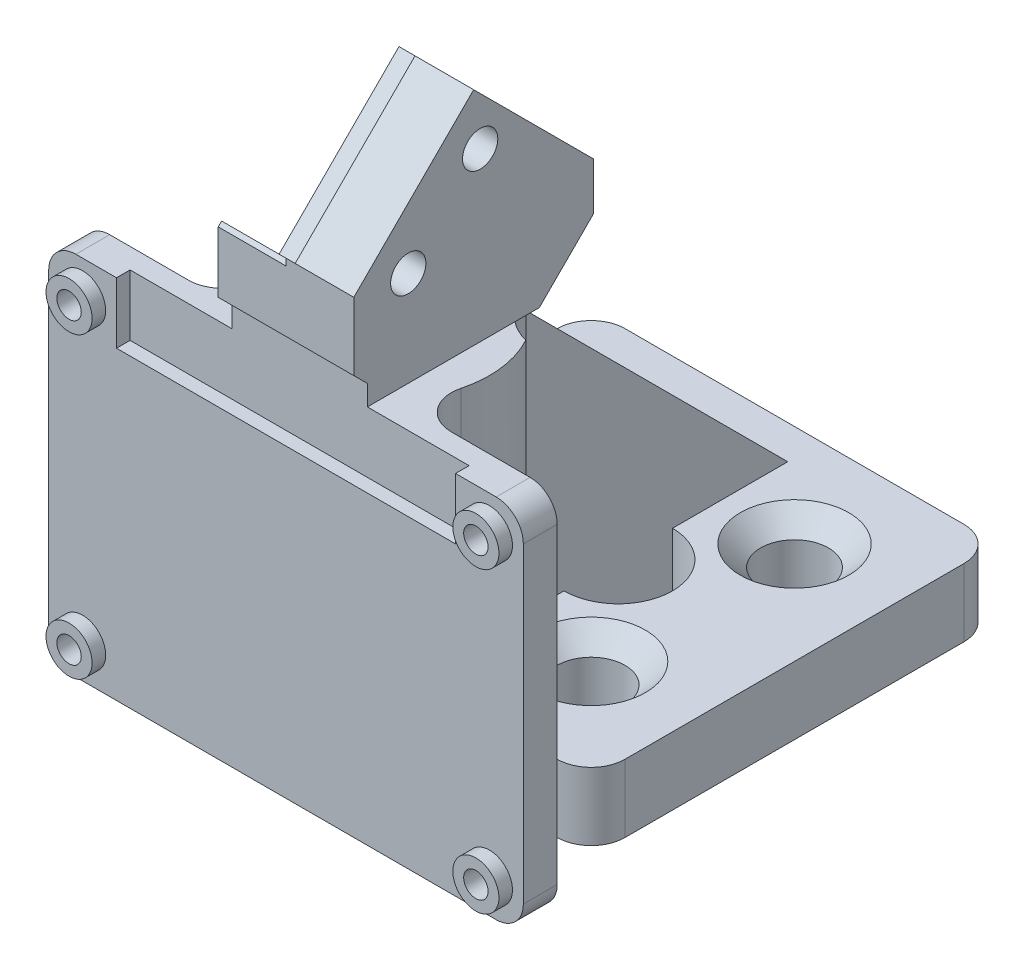
SolidWorks part; units mm, degrees
ref_plane "Front Plane" through (0, 0, 0) normal (0, 0, 1) x (1, 0, 0)
ref_plane "Top Plane" through (0, 0, 0) normal (0, 1, 0) x (1, 0, 0)
ref_plane "Right Plane" through (0, 0, 0) normal (1, 0, 0) x (0, 0, -1)
sketch "Sketch1" plane through (0, 0, 0) normal (0, 1, 0) x (1, 0, 0)
  circle A0 centre (0, 0) radius 15
  dimension "D1" = 30
extrude "Boss-Extrude1" add sketch "Sketch1" along normal blind 54
sketch "Sketch2" plane through (0, 0, 0) normal (1, 0, 0) x (0, 0, -1)
  line L0 (15, 54) -> (-15, 54) construction
  line L1 (-15, 54) -> (20.3553, 54)
  line L2 (-15, 54) -> (-15, 69)
  line L4 (20.3553, 54) -> (20.3553, 69)
  line L5 (-15, 69) -> (2.6777, 86.6777)
  line L6 (2.6777, 86.6777) -> (20.3553, 69)
  point P6 (0, 100)
  dimension "D1" = 25
  dimension "D2" = 15
  dimension "D3" = 15
  dimension "D4" = 45
  dimension "D5" = 15
extrude "Boss-Extrude2" add sketch "Sketch2" along normal mid plane 20
sketch "Sketch4" plane through (0, 42, 42) normal (0, 0.7071, 0.7071) x (1, 0, 0)
  line L0 (10, 38.1838) -> (-10, 38.1838) construction
  line L1 (-12.7, 38.1838) -> (0, 38.1838)
  line L2 (-12.7, 38.1838) -> (-12.7, 63.1838)
  line L3 (-12.7, 63.1838) -> (0, 63.1838)
  line L4 (0, 38.1838) -> (0, 63.1838)
  line L5 (10, 63.1838) -> (-10, 63.1838) construction
  dimension "D1" = 12.7
extrude "Cut-Extrude2" cut sketch "Sketch4" against normal blind 12.7
chamfer "Chamfer1" distance 1 angle 45 1 edges at (-5, 69, 15) first distance on face at (0, 61.5, 15)
sketch "Sketch5" plane through (0, 0, 0) normal (0, -1, 0) x (1, 0, 0)
  circle A0 centre (0, 0) radius 75
  dimension "D1" = 150
sketch "Sketch6" plane through (10, 0, 0) normal (1, 0, 0) x (0, 0, -1)
  line L0 (2.6777, 86.6777) -> (-15, 69) construction
  line L1 (20.3553, 69) -> (2.6777, 86.6777) construction
  line L2 (3.6323, 78.652) -> (-6.9743, 68.0454) construction
  circle A0 centre (3.6323, 78.652) radius 2.6
  circle A1 centre (-6.9743, 68.0454) radius 2.6
  dimension "D4" = 5.2
  dimension "D1" = 6.35
  dimension "D2" = 15
  dimension "D3" = 5
extrude "Cut-Extrude3" cut sketch "Sketch6" against normal through all
sketch "Sketch7" plane through (0, 0, 15) normal (0, 0, 1) x (1, 0, 0)
  line L0 (-31, 0) -> (31, 0)
  line L1 (-35, 4) -> (-35, 50)
  line L2 (-31, 54) -> (31, 54)
  line L3 (35, 4) -> (35, 50)
  line L4 (10, 54) -> (0, 54) construction
  circle A0 centre (-30, 49) radius 1.8
  circle A1 centre (30, 49) radius 1.8
  circle A2 centre (30, 5) radius 1.8
  circle A3 centre (-30, 5) radius 1.8
  arc A4 (31, 54) -> (35, 50) centre (31, 50) cw
  arc A5 (31, 0) -> (35, 4) centre (31, 4) ccw
  arc A6 (-31, 0) -> (-35, 4) centre (-31, 4) cw
  arc A7 (-35, 50) -> (-31, 54) centre (-31, 50) cw
  circle A8 centre (0, 27) radius 5 construction
  point P4 (30, 5)
  point P5 (30, 49)
  point P6 (-30, 49)
  point P7 (-30, 5)
  dimension "D1" = 3.6
  dimension "D2" = 10
  dimension "D3" = 4
  dimension "D4" = 65
  dimension "D5" = 30
  dimension "D6" = 30
  dimension "D7" = 5
  dimension "D8" = 49
  dimension "D9" = 22
  dimension "D10" = 22
  dimension "D11" = 5
extrude "Boss-Extrude4" add sketch "Sketch7" against normal blind 5
fillet "Fillet1" radius 5 2 edges at (-11.1803, 27, 10) (11.1803, 27, 10)
sketch "Sketch8" plane through (0, 0, 0) normal (0, -1, 0) x (1, 0, 0)
  line L1 (30, 0) -> (-30, 0)
  line L2 (30, 0) -> (30, -60)
  line L3 (30, -60) -> (-30, -60)
  line L4 (-30, 0) -> (-30, -60)
  point P4 (0, 0)
  dimension "D1" = 60
  dimension "D2" = 60
extrude "Boss-Extrude5" add sketch "Sketch8" against normal blind 10
sketch "Sketch9" plane through (0, 0, 0) normal (1, 0, 0) x (0, 0, -1)
  line L0 (15, 50) -> (55, 10)
  line L1 (15, 10) -> (15, 54) construction
  line L2 (60, 10) -> (0, 10) construction
  line L3 (15, 50) -> (10, 50)
  line L4 (10, 50) -> (10, 10)
  line L5 (10, 10) -> (55, 10)
  dimension "D1" = 45
  dimension "D2" = 5
  dimension "D3" = 40
extrude "Boss-Extrude6" add sketch "Sketch9" along normal mid plane 8
fillet "Fillet2" radius 5 4 edges at (-30, 5, -60) (30, 5, -60) (-30, 5, 0) (30, 5, 0)
sketch "Sketch10" plane through (0, 10, 0) normal (0, 1, 0) x (1, 0, 0)
  line L0 (-25, 60) -> (25, 60) construction
  line L1 (-15, 45) -> (15, 45) construction
  line L2 (-15, 45) -> (-15, 15) construction
  line L3 (-15, 15) -> (15, 15) construction
  line L4 (15, 45) -> (15, 15) construction
  line L5 (-15, 45) -> (15, 15) construction
  line L6 (-15, 15) -> (15, 45) construction
  circle A0 centre (15, 45) radius 5
  circle A1 centre (-15, 45) radius 5
  circle A2 centre (-15, 15) radius 5
  circle A3 centre (15, 15) radius 5
  point P8 (0, 30)
  dimension "D1" = 10
  dimension "D2" = 30
  dimension "D3" = 30
  dimension "D4" = 30
extrude "Cut-Extrude4" cut sketch "Sketch10" against normal through all
chamfer "Chamfer2" distance 8 angle 45 1 edges at (0, 54, -20.3553)
sketch "Sketch11" plane through (0, 0, 15) normal (0, 0, 1) x (1, 0, 0)
  circle A0 centre (-30, 49) radius 1.8
  circle A1 centre (30, 49) radius 1.8
  circle A2 centre (30, 5) radius 1.8
  circle A3 centre (-30, 5) radius 1.8
  circle A4 centre (-30, 49) radius 1.8 construction
extrude "Extrude-Thin1" add sketch "Sketch11" along normal blind 2 thin thin type one direction wall 1.6
sketch "Sketch12" plane through (0, 0, 15) normal (0, 0, 1) x (1, 0, 0)
  line L0 (-10, 54) -> (-31, 54) construction
  line L1 (-25, 59) -> (25, 59)
  line L2 (-25, 59) -> (-25, 45)
  line L3 (-25, 45) -> (25, 45)
  line L4 (25, 59) -> (25, 45)
  line L5 (-35, 50) -> (-35, 4) construction
  line L6 (35, 4) -> (35, 50) construction
  dimension "D1" = 9
  dimension "D2" = 10
  dimension "D3" = 10
  dimension "D4" = 14
extrude "Cut-Extrude5" cut sketch "Sketch12" against normal blind 2
chamfer "Chamfer3" distance 2 angle 45 1 edges at (0, 59, 13)
sketch "Sketch13" plane through (0, 0, 10) normal (0, 0, -1) x (-1, 0, 0)
  line L649 (-30, 45.8823) -> (-27.3, 47.4412)
  line L650 (-27.3, 47.4412) -> (-27.3, 50.5588)
  line L651 (-27.3, 50.5588) -> (-30, 52.1177)
  line L652 (-30, 52.1177) -> (-32.7, 50.5588)
  line L653 (-32.7, 50.5588) -> (-32.7, 47.4412)
  line L654 (-32.7, 47.4412) -> (-30, 45.8823)
  line L655 (30, 45.8823) -> (32.7, 47.4412)
  line L656 (32.7, 47.4412) -> (32.7, 50.5588)
  line L657 (32.7, 50.5588) -> (30, 52.1177)
  line L658 (30, 52.1177) -> (27.3, 50.5588)
  line L659 (27.3, 50.5588) -> (27.3, 47.4412)
  line L660 (27.3, 47.4412) -> (30, 45.8823)
  line L662 (27.3, 6.5588) -> (27.3, 3.4412)
  line L663 (27.3, 3.4412) -> (30, 1.8823)
  line L664 (30, 1.8823) -> (32.7, 3.4412)
  line L665 (32.7, 3.4412) -> (32.7, 6.5588)
  line L666 (32.7, 6.5588) -> (30, 8.1177)
  line L667 (30, 8.1177) -> (27.3, 6.5588)
  line L668 (-32.7, 6.5588) -> (-32.7, 3.4412)
  line L669 (-32.7, 3.4412) -> (-30, 1.8823)
  line L670 (-30, 1.8823) -> (-27.3, 3.4412)
  line L671 (-27.3, 3.4412) -> (-27.3, 6.5588)
  line L672 (-27.3, 6.5588) -> (-30, 8.1177)
  line L673 (-30, 8.1177) -> (-32.7, 6.5588)
  circle A0 centre (-30, 49) radius 2.7 construction
  circle A1 centre (30, 49) radius 2.7 construction
  circle A2 centre (30, 5) radius 2.7 construction
  circle A3 centre (-30, 5) radius 2.7 construction
  circle A4 centre (-30, 49) radius 1.8 construction
  circle A5 centre (30, 49) radius 1.8 construction
  circle A8 centre (-30, 5) radius 1.8 construction
  circle A9 centre (30, 5) radius 1.8 construction
  dimension "D1" = 5.4
  dimension "D2" = 5.4
  dimension "D3" = 5.4
  dimension "D4" = 5.4
extrude "Cut-Extrude6" cut sketch "Sketch13" against normal blind 2
sketch "Sketch14" plane through (0, 10, 0) normal (0, 1, 0) x (1, 0, 0)
  circle A0 centre (15, 15) radius 8
  circle A1 centre (-15, 15) radius 8
  circle A2 centre (15, 15) radius 5 construction
  dimension "D1" = 16
extrude "Cut-Extrude7" cut sketch "Sketch14" along normal up to surface (44 mm away) up to face at (20.8063, 54, 8.6403)
chamfer "Chamfer4" distance 3 angle 45 4 edges at (-15, 10, -40) (15, 10, -40) (15, 10, -10) (-15, 10, -10)
sketch "Sketch15" plane through (0, 10, 0) normal (0, 1, 0) x (1, 0, 0)
  line L0 (4, 14.4568) -> (4, 55) construction
  line L1 (4, 22) -> (4, 38)
  line L2 (-25, 60) -> (25, 60) construction
  arc A0 (4, 22) -> (4, 38) centre (4, 30) ccw
  dimension "D1" = 8
  dimension "D2" = 30
extrude "Cut-Extrude8" cut sketch "Sketch15" against normal through all
sketch "Sketch16" [suppressed] plane through (0, 42, 42) normal (0, 0.7071, 0.7071) x (1, 0, 0)
  line L1 (10, 63.1838) -> (-10, 63.1838)
  line L2 (10, 63.1838) -> (10, 31.1838)
  line L3 (10, 31.1838) -> (-10, 31.1838)
  line L4 (-10, 63.1838) -> (-10, 31.1838)
  dimension "D1" = 32
extrude "Cut-Extrude9" [suppressed] cut sketch "Sketch16" against normal blind 5.8
sketch "Sketch17" [suppressed] plane through (-10, 0, 0) normal (-1, 0, 0) x (0, 0, 1)
  line L0 (5.4332, 70.3643) -> (0.5542, 65.4853)
  line L1 (10.8988, 64.8988) -> (-6.7789, 82.5765) construction
  line L2 (-11.6579, 77.6974) -> (6.0197, 60.0197) construction
  line L3 (0.5542, 65.4853) -> (9.0395, 57)
  line L4 (9.0395, 57) -> (13, 57)
  line L5 (5.4332, 70.3643) -> (15.8988, 59.8988)
  line L6 (15.8988, 59.8988) -> (13, 57)
  dimension "D1" = 12
extrude "Cut-Extrude10" [suppressed] cut sketch "Sketch17" against normal through all
sketch "Sketch18" [suppressed] plane through (0, 33.0197, 33.0197) normal (0, 0.7071, 0.7071) x (1, 0, 0)
  line L0 (-6.35, 53.1838) -> (-6.35, 63.1838) construction
  line L1 (10, 63.1838) -> (6.7267, 63.1838)
  line L2 (10, 63.1838) -> (10, 53.1838)
  line L3 (10, 53.1838) -> (6.7267, 53.1838)
  line L4 (-22.7, 63.1838) -> (-22.7, 53.1838)
  line L5 (-19.4267, 53.1838) -> (-22.7, 53.1838)
  line L6 (-19.4267, 63.1838) -> (-22.7, 63.1838)
  line L7 (6.7267, 53.1838) -> (-19.4267, 53.1838) construction
  arc A4 (6.7267, 63.1838) -> (-19.4267, 63.1838) centre (-6.35, 58.1838) ccw
  arc A5 (6.7267, 53.1838) -> (-19.4267, 53.1838) centre (-6.35, 58.1838) cw
  point P8 (10, 58.1838)
  point P12 (-6.35, 63.1838)
  point P15 (-6.35, 53.1838)
  dimension "D3" = 14
  dimension "D1" = 5
  dimension "D2" = 32.7
extrude "Boss-Extrude7" [suppressed] add sketch "Sketch18" along normal up to surface (6.9 mm away) up to face at (5, 77.8388, 6.1612)
sketch "Sketch19" [suppressed] plane through (0, 20.8223, 20.8223) normal (0, -0.7071, -0.7071) x (1, 0, 0)
  line L0 (10, -46.9203) -> (10, -58.234) construction
  line L1 (-22.7, -63.1838) -> (-22.7, -53.1838) construction
  line L2 (6.25, -55.1838) -> (10, -55.1838)
  line L3 (3.25, -58.1838) -> (3.25, -63.1838)
  line L4 (6.7267, -63.1838) -> (-10, -63.1838) construction
  line L5 (10, -55.1838) -> (10, -63.1838)
  line L6 (10, -63.1838) -> (3.25, -63.1838)
  arc A0 (6.25, -55.1838) -> (3.25, -58.1838) centre (6.25, -58.1838) ccw
  point P4 (-22.7, -58.1838)
  dimension "D2" = 3
  dimension "D1" = 3.75
extrude "Cut-Extrude11" [suppressed] cut sketch "Sketch19" against normal up to surface (17.2497 mm away) up to face at (-5, 68.8586, -2.8191)
sketch "Sketch20" [suppressed] plane through (0, 33.0197, 33.0197) normal (0, -0.7071, -0.7071) x (1, 0, 0)
  line L0 (6.25, -58.1838) -> (-18.95, -58.1838) construction
  line L1 (-22.7, -63.1838) -> (-22.7, -53.1838) construction
  line L2 (10, -55.1838) -> (10, -63.1838) construction
  circle A0 centre (6.25, -58.1838) radius 1.5
  circle A1 centre (-18.95, -58.1838) radius 1.5
  point P5 (-22.7, -58.1838)
  dimension "D3" = 3
  dimension "D1" = 3.75
  dimension "D2" = 3.75
extrude "Cut-Extrude12" [suppressed] cut sketch "Sketch20" against normal through all
chamfer "Chamfer5" [suppressed] distance 7 angle 45
sketch "Sketch21" [suppressed] plane through (0, 0, 0) normal (0, 0, 1) x (1, 0, 0)
  line L0 (-10, 54) -> (-15, 54)
  line L1 (-15, 54) -> (-23.25, 62.25)
  line L2 (-23.25, 62.25) -> (-23.25, 75.5054)
  line L3 (-23.25, 75.5054) -> (-10, 75.5054)
  line L4 (-10, 54) -> (-10, 75.5054)
  line L5 (-19.4267, 75.5054) -> (-22.7, 75.5054) construction
  dimension "D1" = 45
  dimension "D2" = 13.25
extrude "Boss-Extrude8" [suppressed] add sketch "Sketch21" against normal blind 5
sketch "Sketch22" [suppressed] plane through (0, 33.0197, 33.0197) normal (0, -0.7071, -0.7071) x (1, 0, 0)
  line L0 (-23.25, -56.9259) -> (-23.25, -47.5529) construction
  line L2 (10, -63.1838) -> (10, -49.1838)
  line L3 (10, -49.1838) -> (10.7, -49.1838)
  line L4 (10.7, -63.1838) -> (10.7, -49.1838)
  line L6 (-22.7, -63.1838) -> (-22.7, -53.1838)
  line L7 (-22.7, -53.1838) -> (-23.25, -53.1838)
  line L8 (-23.25, -63.1838) -> (-23.25, -53.1838)
  line L9 (-19.4267, -63.1838) -> (-22.7, -63.1838) construction
  line L10 (-18.25, -63.1838) -> (-22.7, -63.1838)
  line L11 (-18.25, -63.1838) -> (-18.25, -65.1838)
  line L12 (-18.25, -65.1838) -> (-23.25, -65.1838)
  line L13 (-23.25, -63.1838) -> (-23.25, -65.1838)
  line L15 (10, -63.1838) -> (5.7, -63.1838)
  line L16 (10.7, -63.1838) -> (10.7, -65.1838)
  line L17 (10.7, -65.1838) -> (5.7, -65.1838)
  line L18 (5.7, -63.1838) -> (5.7, -65.1838)
  dimension "D1" = 0.7
  dimension "D2" = 14
  dimension "D3" = 2
  dimension "D4" = 5
extrude "Boss-Extrude9" [suppressed] add sketch "Sketch22" against normal up to surface (6.9 mm away) up to face at (5, 77.8388, 6.1612)
sketch "Sketch23" [suppressed] plane through (-23.25, 0, 0) normal (-1, 0, 0) x (0, 0, 1)
  line L0 (-8.1931, 83.9907) -> (-13.0721, 79.1116) construction
  line L1 (-5, 62.25) -> (0, 62.25) construction
  line L2 (-11.6579, 77.6974) -> (-6.7789, 82.5765) construction
  line L3 (-5, 71.0395) -> (-13.0721, 79.1116) construction
  line L4 (-18.0219, 84.0614) -> (-13.0721, 79.1116) construction
  line L5 (-8.1931, 83.9907) -> (0.2922, 75.5054) construction
  line L6 (-5, 65.25) -> (0, 65.25) construction
  line L7 (-5, 71.0395) -> (-5, 62.25) construction
  line L8 (0, 75.2132) -> (0, 62.25) construction
  circle A0 centre (-2.5, 65.25) radius 0.75
  circle A1 centre (-9.2184, 80.1369) radius 0.75
  dimension "D3" = 1.5
  dimension "D1" = 2
  dimension "D2" = 3
extrude "Cut-Extrude13" [suppressed] cut sketch "Sketch23" against normal blind 5
sketch "Sketch24" [suppressed] plane through (10.7, 0, 0) normal (1, 0, 0) x (0, 0, -1)
  line L0 (-0.9993, 74.7983) -> (3.8798, 69.9192) construction
  line L1 (13.0721, 79.1116) -> (1.7584, 67.7979) construction
  line L2 (-3.1206, 72.677) -> (8.1931, 83.9907) construction
  line L3 (-3.1206, 72.677) -> (1.7584, 67.7979) construction
  line L4 (6.0718, 81.8693) -> (10.9508, 76.9903) construction
  line L5 (-3.1206, 72.677) -> (8.1931, 83.9907) construction
  line L6 (13.0721, 79.1116) -> (1.7584, 67.7979) construction
  line L7 (8.1931, 83.9907) -> (13.0721, 79.1116) construction
  circle A0 centre (1.4402, 72.3588) radius 0.75
  circle A1 centre (8.5113, 79.4298) radius 0.75
  dimension "D2" = 1.5
  dimension "D1" = 3
  dimension "D3" = 3
extrude "Cut-Extrude14" [suppressed] cut sketch "Sketch24" against normal blind 5
sketch "Sketch25" [suppressed] plane through (0, 0, -20.3553) normal (0, 0, -1) x (-1, 0, 0)
  line L0 (3.375, 62) -> (3.375, 69) construction
  line L1 (-3.25, 62) -> (10, 62) construction
  line L2 (-3.25, 69) -> (10, 69) construction
  circle A0 centre (3.375, 65.5) radius 0.75
  dimension "D1" = 1.5
extrude "Cut-Extrude15" [suppressed] cut sketch "Sketch25" against normal blind 5
sketch "Sketch26" plane through (0, 33.0197, 33.0197) normal (0, 0.7071, 0.7071) x (1, 0, 0)
  line L0 (0, 60.7838) -> (0, 55.5838) construction
  line L1 (0, 45.7838) -> (0, 40.5838) construction
  line L3 (0, 38.1838) -> (0, 63.1838) construction
  circle A0 centre (-5, 58.1838) radius 2.5
  circle A1 centre (-5, 43.1838) radius 2.5
  point P4 (0, 0)
  point P5 (0, 58.1838)
  point P8 (0, 43.1838)
  point P11 (0, 0)
  point P12 (0, 0)
  point P13 (0, 0)
  point P14 (0, 0)
  point P17 (0, 0)
  point P18 (0, 0)
  dimension "D1" = 5
  dimension "D2" = 5
extrude "Cut-Extrude16" cut sketch "Sketch26" against normal blind 37
sketch "Sketch27" plane through (-10, 0, 0) normal (-1, 0, 0) x (0, 0, 1)
  line L0 (-20.3553, 62) -> (-6.1777, 47.8223)
  line L1 (-6.1777, 47.8223) -> (-27.3909, 26.6091)
  line L2 (-27.3909, 26.6091) -> (-41.5685, 40.7868)
  line L3 (-41.5685, 40.7868) -> (-20.3553, 62)
  line L4 (6.0197, 60.0197) -> (-6.1777, 47.8223) construction
  line L5 (-20.3553, 62) -> (-12.3553, 54) construction
  point P9 (-19.6538, 34.3462)
  dimension "D1" = 30
extrude "Cut-Extrude17" cut sketch "Sketch27" against normal blind 9
chamfer "Chamfer6" distance 3 angle 45 1 edges at (-4, 29.3591, -30.1409)
sketch "Sketch29" plane through (0, 42, 42) normal (0, 0.7071, 0.7071) x (1, 0, 0)
  line L0 (10, 63.1838) -> (0, 63.1838) construction
  line L1 (0, 38.1838) -> (1.35, 38.1838)
  line L2 (0, 38.1838) -> (0, 63.1838)
  line L3 (0, 63.1838) -> (1.35, 63.1838)
  line L4 (1.35, 38.1838) -> (1.35, 63.1838)
  line L5 (10, 38.1838) -> (0, 38.1838) construction
  point P5 (1.8635, 63.1838)
  point P8 (1.28, 38.1838)
  point P11 (1.35, 38.1838)
extrude "Cut-Extrude18" cut sketch "Sketch29" against normal blind 12.7
